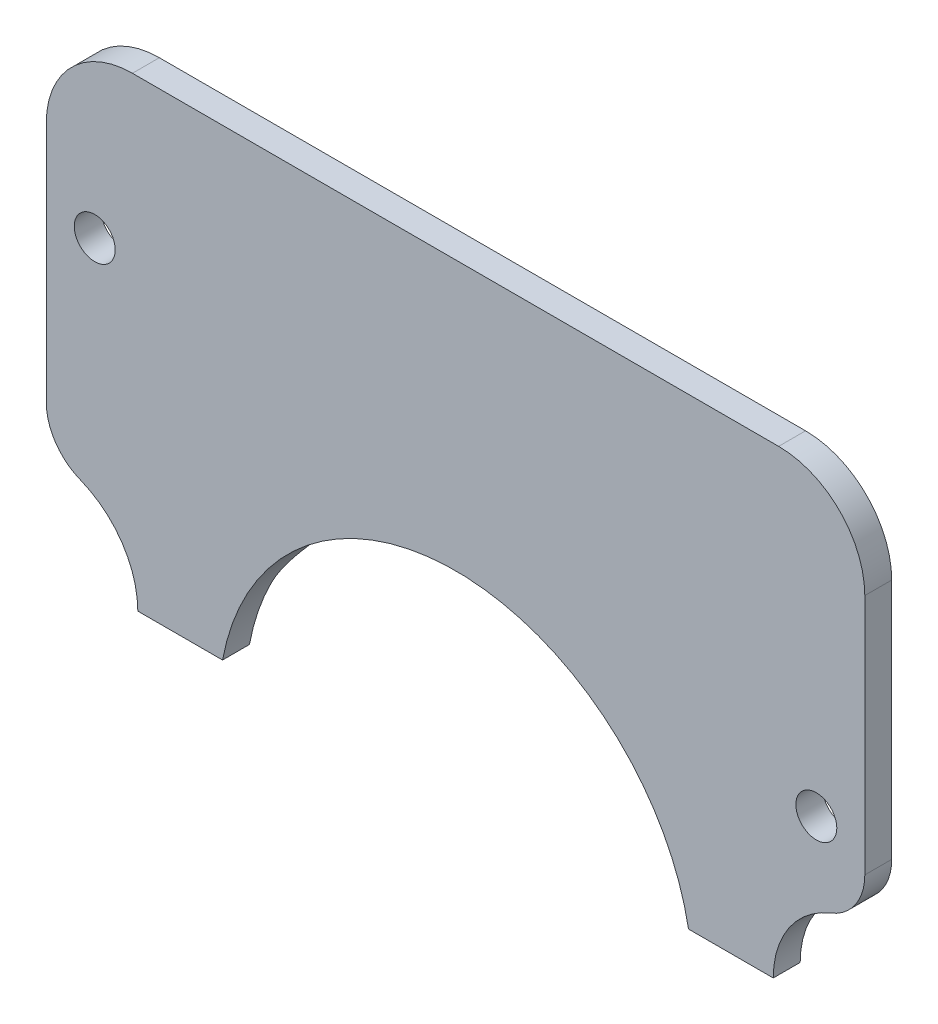
SolidWorks part; units mm, degrees
ref_plane "Front Plane" through (0, 0, 0) normal (0, 0, 1) x (1, 0, 0)
ref_plane "Top Plane" through (0, 0, 0) normal (0, 1, 0) x (1, 0, 0)
ref_plane "Right Plane" through (0, 0, 0) normal (1, 0, 0) x (0, 0, -1)
sketch "Sketch1" plane through (0, 0, 0) normal (0, 0, 1) x (1, 0, 0)
  line L0 (-38, 4) -> (38, 4)
  line L1 (38, 4) -> (38, 47)
  line L2 (38, 47) -> (-38, 47)
  line L3 (-38, 47) -> (-38, 4)
  circle A0 centre (0, 0) radius 17
  circle A1 centre (0, 0) radius 22
  circle A2 centre (0, 0) radius 29
  dimension "D1" = 34
  dimension "D2" = 5
  dimension "D4" = 7
  dimension "D3" = 4
  dimension "D5" = 38
  dimension "D6" = 38
  dimension "D7" = 43
extrude "Boss-Extrude1" add sketch "Sketch1" along normal blind 2.5 contours L0 A2 A1 | A2 L0 L1 L2 L3 region at (0, 31.0053, 0) region at (0, 28.3735, 0)
sketch "Sketch2" plane through (0, 0, 2.5) normal (0, 0, 1) x (1, 0, 0)
  line L0 (21.6333, 4) -> (38, 4) construction
  line L1 (38, 4) -> (38, 47) construction
  line L2 (-38, 47) -> (-38, 4) construction
  line L3 (38, 47) -> (-38, 47) construction
  circle A0 centre (33.5, 19) radius 1.9
  circle A1 centre (-33.5, 32) radius 1.9
  dimension "D1" = 3.8
  dimension "D2" = 3.8
  dimension "D3" = 15
  dimension "D4" = 4.5
  dimension "D5" = 3.8
  dimension "D6" = 4.5
  dimension "D7" = 15
extrude "Cut-Extrude1" cut sketch "Sketch2" against normal blind 3.5
sketch "Sketch3" plane through (0, 0, 2.5) normal (0, 0, 1) x (1, 0, 0)
  circle A0 centre (-38, 4) radius 8.5
  circle A1 centre (38, 4) radius 8.5
  dimension "D1" = 17
  dimension "D2" = 17
extrude "Cut-Extrude2" cut sketch "Sketch3" against normal up to surface (2.5 mm away) up to face at (35.4, 19, 0)
fillet "Fillet2" radius 5 2 edges at (-38, 12.5, 1.25) (38, 12.5, 1.25)
fillet "Fillet3" radius 8 2 edges at (-38, 47, 1.25) (38, 47, 1.25)
sketch "Sketch4" plane through (0, 0, 0) normal (0, 0, -1) x (-1, 0, 0)
  line L0 (-18.735, 15) -> (-16.0935, 15)
  line L1 (29.5, 4) -> (21.6333, 4) construction
  line L2 (16.0935, 15) -> (18.735, 15)
  arc A0 (21.6333, 4) -> (-21.6333, 4) centre (0, 0) ccw construction
  arc A1 (16.0935, 15) -> (-16.0935, 15) centre (0, 0) ccw
  arc A2 (18.735, 15) -> (-18.735, 15) centre (0, 0) ccw
  dimension "D1" = 2
  dimension "D2" = 11
  dimension "D3" = 11
extrude "Boss-Extrude2" add sketch "Sketch4" along normal blind 8 contours A1 L0 A2 L2
fillet "Fillet4" radius 3 1 edges at (0, 24, 0)
fillet "Fillet5" radius 5 2 edges at (-19.2717, 15, 0) (19.2717, 15, 0)
fillet "Fillet6" radius 5 2 edges at (-17.4142, 15, -8) (17.4142, 15, -8)
